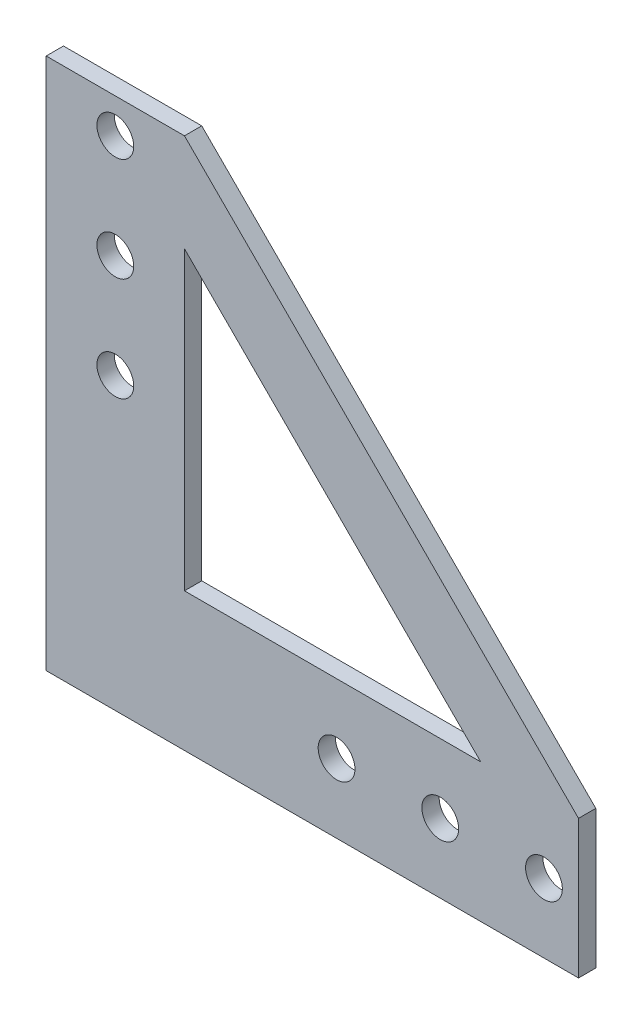
SolidWorks part; units mm, degrees
ref_plane "Front Plane" through (0, 0, 0) normal (0, 0, 1) x (1, 0, 0)
ref_plane "Top Plane" through (0, 0, 0) normal (0, 1, 0) x (1, 0, 0)
ref_plane "Right Plane" through (0, 0, 0) normal (1, 0, 0) x (0, 0, -1)
sketch "Sketch1" plane through (0, 0, 0) normal (0, 0, 1) x (1, 0, 0)
  line L0 (25.4, 97.79) -> (97.79, 25.4)
  line L1 (0, 0) -> (25.4, 0)
  line L2 (0, 0) -> (0, 97.79)
  line L3 (0, 97.79) -> (25.4, 97.79)
  line L4 (25.4, 25.4) -> (25.4, 79.8295)
  line L5 (0, 0) -> (97.79, 0)
  line L6 (0, 0) -> (0, 25.4)
  line L7 (25.4, 25.4) -> (79.8295, 25.4)
  line L8 (97.79, 0) -> (97.79, 25.4)
  line L9 (25.4, 79.8295) -> (79.8295, 25.4)
  line L10 (16.4197, 88.8097) -> (88.8097, 16.4197) construction
  dimension "D1" = 25.4
  dimension "D2" = 25.4
  dimension "D3" = 97.79
  dimension "D4" = 97.79
  dimension "D6" = 45
  dimension "D7" = 17.9605
  dimension "D5" = 12.7
extrude "Boss-Extrude1" add sketch "Sketch1" along normal blind 3.175 contours L5 L8 L7 L4 L3 L2 L1 region at (60.6171, 60.6171, 0)
sketch "Sketch2" plane through (0, 0, 3.175) normal (0, 0, 1) x (1, 0, 0)
  line L0 (0, 0) -> (97.79, 0) construction
  line L1 (0, 0) -> (0, 97.79) construction
  line L2 (25.4, 25.4) -> (79.8295, 25.4) construction
  circle A0 centre (53.34, 12.7) radius 3.3782
  circle A1 centre (72.39, 12.7) radius 3.3782
  circle A2 centre (12.7, 53.34) radius 3.3782
  circle A3 centre (12.7, 72.39) radius 3.3782
  circle A4 centre (12.7, 91.44) radius 3.3782
  circle A5 centre (91.44, 12.7) radius 3.3782
  dimension "D5" = 6.7564
  dimension "D6" = 6.7564
  dimension "D7" = 6.7564
  dimension "D8" = 6.7564
  dimension "D9" = 6.7564
  dimension "D10" = 6.7564
  dimension "D1" = 53.34
  dimension "D2" = 53.34
  dimension "D3" = 19.05
  dimension "D4" = 19.05
  dimension "D11" = 19.05
  dimension "D12" = 19.05
  dimension "D13" = 12.7
  dimension "D14" = 12.7
  dimension "D15" = 12.7
  dimension "D16" = 12.7
  dimension "D17" = 12.7
  dimension "D18" = 12.7
extrude "Cut-Extrude1" cut sketch "Sketch2" against normal through all
